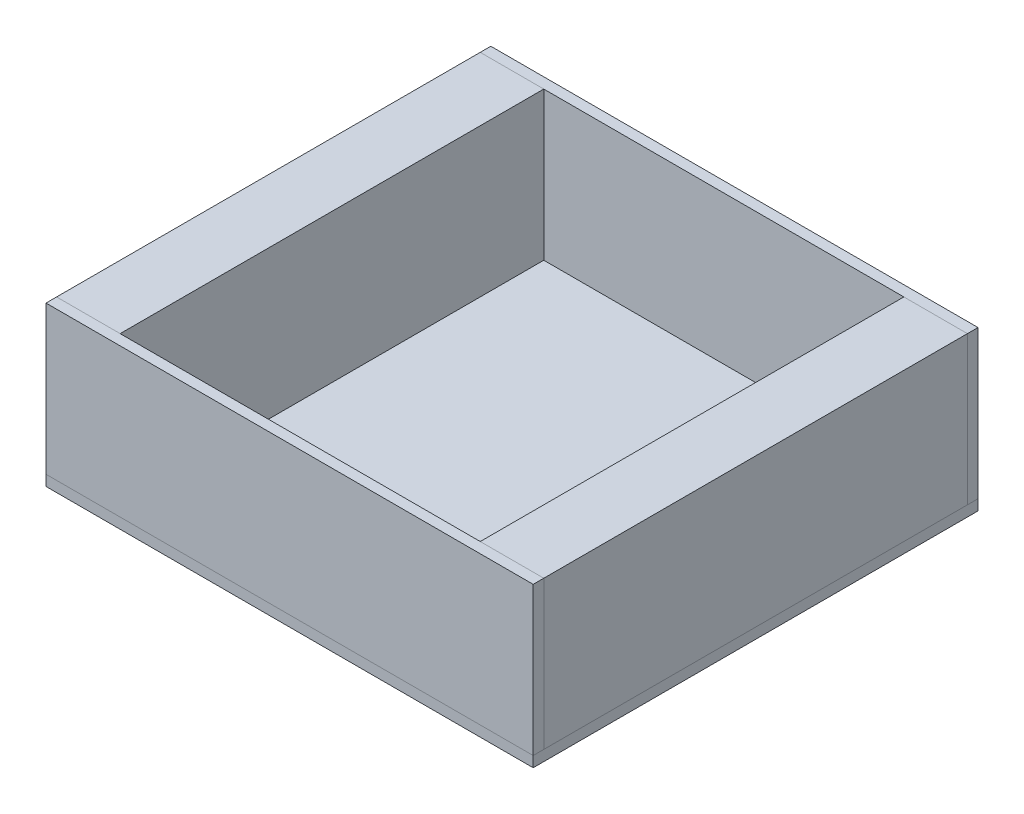
SolidWorks part; units mm, degrees
material "Pine"
ref_plane "Front Plane" through (0, 0, 0) normal (0, 0, 1) x (1, 0, 0)
ref_plane "Top Plane" through (0, 0, 0) normal (0, 1, 0) x (1, 0, 0)
ref_plane "Right Plane" through (0, 0, 0) normal (1, 0, 0) x (0, 0, -1)
sketch "Sketch1" plane through (0, 0, 0) normal (0, 0, 1) x (1, 0, 0)
  line L1 (-19.05, -44.45) -> (19.05, -44.45)
  line L2 (-19.05, -44.45) -> (-19.05, 44.45)
  line L3 (-19.05, 44.45) -> (19.05, 44.45)
  line L4 (19.05, -44.45) -> (19.05, 44.45)
  line L5 (-19.05, -44.45) -> (19.05, 44.45) construction
  line L6 (-19.05, 44.45) -> (19.05, -44.45) construction
  line L7 (234.95, -44.45) -> (273.05, -44.45)
  line L8 (234.95, -44.45) -> (234.95, 44.45)
  line L9 (234.95, 44.45) -> (273.05, 44.45)
  line L10 (273.05, -44.45) -> (273.05, 44.45)
  line L11 (234.95, -44.45) -> (273.05, 44.45) construction
  line L12 (234.95, 44.45) -> (273.05, -44.45) construction
  point P0 (0, 0)
  point P5 (254, 0)
  point P11 (0, 0)
  dimension "D1" = 88.9
  dimension "D2" = 38.1
  dimension "D3" = 88.9
  dimension "D4" = 38.1
  dimension "D5" = 254
extrude "Boss-Extrude1" add sketch "Sketch1" along normal blind 254
sketch "Sketch2" plane through (0, 0, 0) normal (0, 0, 1) x (1, 0, 0)
  line L1 (-19.05, -44.45) -> (273.05, -44.45)
  line L2 (-19.05, -44.45) -> (-19.05, 44.45)
  line L3 (-19.05, 44.45) -> (273.05, 44.45)
  line L4 (273.05, -44.45) -> (273.05, 44.45)
extrude "Boss-Extrude2" add sketch "Sketch2" against normal blind 6.35 separate body
extrude "Boss-Extrude3" add sketch "Sketch2<2>" along normal blind 6.35 from surface separate body starting at face at (0, 0, 254)
sketch "Sketch2<2>" plane through (0, 0, 0) normal (0, 0, 1) x (1, 0, 0) same geometry as "Sketch2"
sketch "Sketch3" plane through (0, 0, 0) normal (0, 1, 0) x (1, 0, 0)
  line L1 (-19.05, 6.35) -> (273.05, 6.35)
  line L2 (-19.05, 6.35) -> (-19.05, -260.35)
  line L3 (-19.05, -260.35) -> (273.05, -260.35)
  line L4 (273.05, 6.35) -> (273.05, -260.35)
  point P4 (0, 0)
  point P5 (-19.05, 6.35)
  point P8 (273.05, -260.35)
  point P10 (0, 0)
  point P12 (0, 0)
extrude "Boss-Extrude4" add sketch "Sketch3" against normal blind 6.35 from surface separate body starting at face at (0, -44.45, 127)
